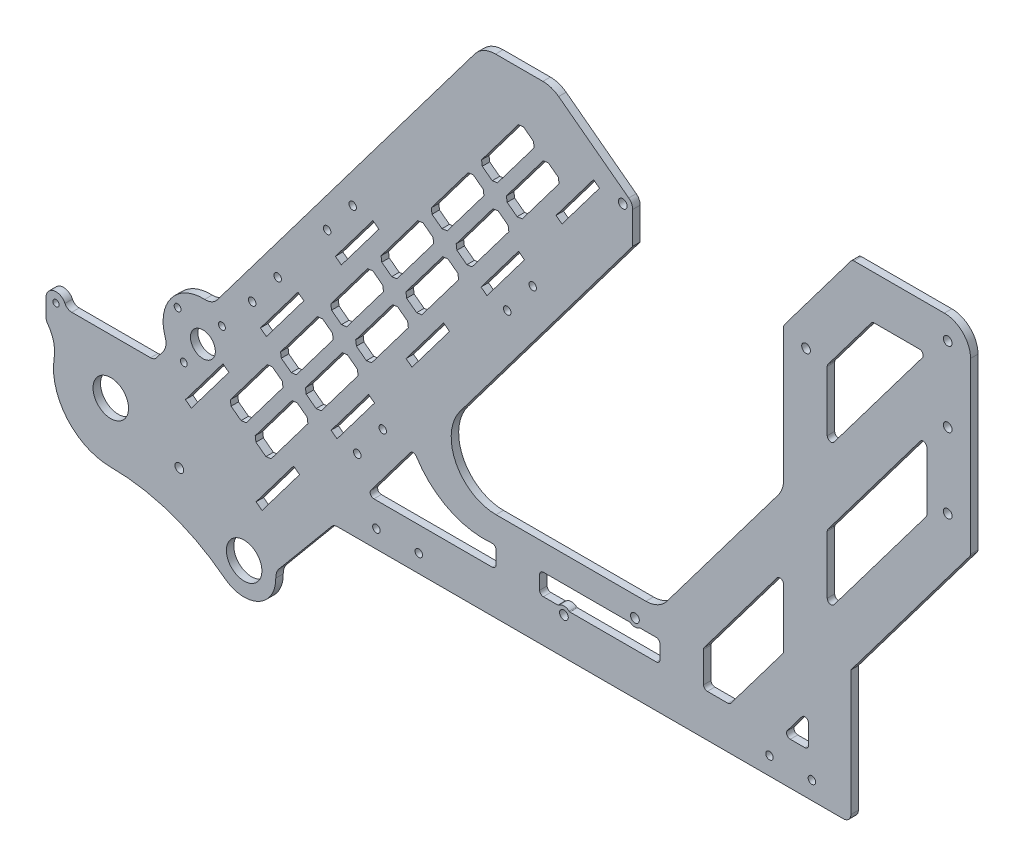
SolidWorks part; units mm, degrees
material "Liga 1060"
ref_plane "Plano frontal" through (0, 0, 0) normal (0, 0, 1) x (1, 0, 0)
ref_plane "Plano superior" through (0, 0, 0) normal (0, 1, 0) x (1, 0, 0)
ref_plane "Plano direito" through (0, 0, 0) normal (1, 0, 0) x (0, 0, -1)
sketch "Esboço1" plane through (0, 0, 0) normal (0, 0, 1) x (1, 0, 0)
  line L0 (0, 92) -> (0, 0) construction
  line L1 (0, 0) -> (52, 0)
  line L4 (231, 49.5601) -> (742, 49.5601)
  line L5 (742, 49.5601) -> (742, 441.5601)
  line L6 (742, 441.5601) -> (350.3481, 441.5601)
  line L7 (350.3481, 441.5601) -> (86.9357, 92)
  line L8 (0, 92) -> (86.9357, 92)
  line L9 (0, 92) -> (0, 0)
  circle A0 centre (52, 48) radius 14.25
  arc A1 (52, 0) -> (143.3633, -31.4562) centre (52, -148.4086) cw
  circle A2 centre (52, 48) radius 50.8 construction
  circle A3 centre (159, -11.4399) radius 25.4 construction
  arc A5 (183.9836, -6.8596) -> (231, 49.5601) centre (231, 1.7601) cw
  circle A6 centre (159, -11.4399) radius 14.25
  arc A7 (143.3633, -31.4562) -> (183.9836, -6.8596) centre (159, -11.4399) ccw
  dimension "D1" = 28.5
  dimension "D5" = 101.6
  dimension "D7" = 50.8
  dimension "D9" = 61
  dimension "D11" = 48
  dimension "D12" = 72
  dimension "D2" = 107
  dimension "D3" = 52
  dimension "D4" = 127
  dimension "D6" = 52
  dimension "D8" = 92
  dimension "D10" = 59.4399
  dimension "D13" = 742
  dimension "D16" = 86.9357
  dimension "D17" = 392
extrude "Ressalto-extrusão1" add sketch "Esboço1" along normal blind 6 contours A0 | A6 | L4 L5 L6 L7 L8 L9 L1 A1 A7 A5 region at (52, 48, 0) region at (159, -11.4399, 0)
sketch "Esboço2" plane through (0, 0, 6) normal (0, 0, 1) x (1, 0, 0)
  line L0 (183.9836, -6.8596) -> (231, 49.5601)
  arc A0 (183.9836, -6.8596) -> (231, 49.5601) centre (231, 1.7601) cw
extrude "Ressalto-extrusão2" add sketch "Esboço2" against normal through all
fillet "Filete1" radius 12 1 edges at (183.9836, -6.8596, 3)
fillet "Filete2" radius 6 2 edges at (231, 49.5601, 3) (86.9357, 92, 3)
sketch "Esboço3" plane through (0, 0, 6) normal (0, 0, 1) x (1, 0, 0)
  line L0 (52, 92) -> (0, 92)
  line L1 (0, 92) -> (0, 0)
  line L2 (52, 0) -> (0, 0)
  circle A0 centre (52, 48) radius 44 construction
  arc A1 (52, 0) -> (52, 92) centre (52, 46) cw
  arc A2 (143.3633, -31.4562) -> (52, 0) centre (52, -148.4086) ccw construction
  circle A3 centre (8, 84) radius 6.35 construction
  circle A4 centre (8, 84) radius 2.5 construction
  arc A5 (0, 76) -> (6.5667, 53.1986) centre (-21.0883, 57.5803) cw
  line M17 (0, 0) -> (52, 0)
  dimension "D1" = 12.7
  dimension "D2" = 8
  dimension "D4" = 5
  dimension "D6" = 28
  dimension "D3" = 8
  dimension "D5" = 16
extrude "Corte-extrusão1" cut sketch "Esboço3" against normal blind 10 contours A5 L1 A1 M17 | A4 region at (9.7589, 23.0045, 6)
fillet "Filete3" radius 6 1 edges at (0, 76, 3)
sketch "Esboço5" plane through (0, 0, 6) normal (0, 0, 1) x (1, 0, 0)
  line L0 (0, 92) -> (83.9442, 92) construction
  line L1 (0, 92) -> (0, 78.1284) construction
  line L2 (0, 92) -> (16, 92)
  arc A0 (0, 92) -> (16, 92) centre (8, 92) cw
  dimension "D1" = 8
extrude "Ressalto-extrusão3" add sketch "Esboço5" against normal through all
sketch "Esboço6" plane through (0, 0, 6) normal (0, 0, 1) x (1, 0, 0)
  circle A0 centre (8, 92) radius 2.5
  dimension "D1" = 5
extrude "Corte-extrusão2" cut sketch "Esboço6" against normal blind 10
fillet "Filete4" radius 6 1 edges at (16, 92, 3)
sketch "Esboço7" plane through (0, 0, 6) normal (0, 0, 1) x (1, 0, 0)
  line L0 (88.736, 94.3891) -> (168.5995, 34.2076) construction
  line L1 (88.736, 94.3891) -> (350.3481, 441.5601) construction
  line L2 (168.5995, 34.2076) -> (430.2117, 381.3786) construction
  line L3 (350.3481, 441.5601) -> (430.2117, 381.3786) construction
  line L4 (168.5995, 34.2076) -> (198.6903, 74.1394)
  line L5 (168.5995, 34.2076) -> (173.3913, 30.5967)
  line L6 (198.6903, 74.1394) -> (203.4821, 70.5285)
  line L7 (173.3913, 30.5967) -> (203.4821, 70.5285)
  line L8 (228.781, 114.0712) -> (258.8718, 154.0029)
  line L9 (228.781, 114.0712) -> (233.5728, 110.4603)
  line L10 (233.5728, 110.4603) -> (263.6636, 150.392)
  line L11 (258.8718, 154.0029) -> (263.6636, 150.392)
  line L12 (288.9625, 193.9347) -> (319.0533, 233.8665)
  line L13 (288.9625, 193.9347) -> (293.7543, 190.3238)
  line L14 (293.7543, 190.3238) -> (323.8451, 230.2556)
  line L15 (319.0533, 233.8665) -> (323.8451, 230.2556)
  line L16 (349.144, 273.7983) -> (379.2348, 313.73)
  line L17 (349.144, 273.7983) -> (353.9359, 270.1874)
  line L18 (353.9359, 270.1874) -> (384.0266, 310.1191)
  line L19 (379.2348, 313.73) -> (384.0266, 310.1191)
  line L20 (409.3255, 353.6618) -> (439.4163, 393.5936)
  line L21 (409.3255, 353.6618) -> (414.1174, 350.0509)
  line L22 (414.1174, 350.0509) -> (444.2081, 389.9827)
  line L23 (439.4163, 393.5936) -> (444.2081, 389.9827)
  line L24 (111.8964, 76.9365) -> (141.9872, 116.8682)
  line L25 (111.8964, 76.9365) -> (116.6882, 73.3256)
  line L26 (116.6882, 73.3256) -> (146.779, 113.2574)
  line L27 (141.9872, 116.8682) -> (146.779, 113.2574)
  line L28 (172.0779, 156.8) -> (202.1687, 196.7318)
  line L29 (202.1687, 196.7318) -> (206.9605, 193.1209)
  line L30 (176.8697, 153.1891) -> (206.9605, 193.1209)
  line L31 (172.0779, 156.8) -> (176.8697, 153.1891)
  line L32 (232.2594, 236.6636) -> (262.3502, 276.5954)
  line L33 (262.3502, 276.5954) -> (267.142, 272.9845)
  line L34 (237.0512, 233.0527) -> (267.142, 272.9845)
  line L35 (232.2594, 236.6636) -> (237.0512, 233.0527)
  circle A0 centre (159, -11.4399) radius 25.4 construction
  circle A1 centre (159, -11.4399) radius 30 construction
  dimension "D2" = 50.8
  dimension "D3" = 60
  dimension "D1" = 100
  dimension "D4" = 50
  dimension "D5" = 6
  dimension "D7" = 2
  dimension "D6" = 5
  dimension "D8" = 3
extrude "Corte-extrusão3" cut sketch "Esboço7" against normal through all
sketch "Esboço8" plane through (0, 0, 6) normal (0, 0, 1) x (1, 0, 0)
  circle A0 centre (711, 628) radius 14.25
  circle A2 centre (52, 48) radius 14.25 construction
  circle A3 centre (711, 628) radius 16
  dimension "D3" = 28.5
  dimension "D4" = 32
  dimension "D1" = 659
  dimension "D2" = 580
extrude "Ressalto-extrusão4" add sketch "Esboço8" against normal blind 6 separate body
sketch "Esboço9" plane through (0, 0, 0) normal (0, 0, -1) x (-1, 0, 0)
  line L0 (-742, 441.5601) -> (-350.3481, 441.5601) construction
  line L1 (-592, 441.5601) -> (-492, 441.5601)
  line L2 (-742, 49.5601) -> (-742, 441.5601) construction
  line L3 (-492, 441.5601) -> (-250.8627, 121.5601)
  line L4 (-353.9359, 270.1874) -> (-384.0266, 310.1191) construction
  line L6 (-592, 121.5601) -> (-250.8627, 121.5601)
  line L7 (-592, 441.5601) -> (-592, 121.5601)
  dimension "D3" = 320
  dimension "D1" = 150
  dimension "D2" = 100
extrude "Corte-extrusão4" cut sketch "Esboço9" against normal through all
fillet "Filete5" radius 55 1 edges at (250.8627, 121.5601, 3)
sketch "Esboço10" plane through (0, 0, 0) normal (0, 0, -1) x (-1, 0, 0)
  line L0 (-233.8102, 49.5601) -> (-742, 49.5601) construction
  line L1 (-742, 49.5601) -> (-742, 441.5601) construction
  line L2 (-646, 49.5601) -> (-742, 49.5601)
  line L3 (-742, 49.5601) -> (-742, 245.5601)
  line L4 (-742, 49.5601) -> (-742, 441.5601) construction
  line L6 (-646, 176.7664) -> (-646, 49.5601)
  arc A4 (-742, 245.5601) -> (-646, 176.7664) centre (-830.0314, 21.3346) cw
  dimension "D1" = 96
extrude "Corte-extrusão5" cut sketch "Esboço10" against normal through all
fillet "Filete8" radius 21 3 edges at (742, 441.5601, 3) (350.3481, 441.5601, 3) (492, 441.5601, 3)
sketch "Esboço12" plane through (0, 0, 6) normal (0, 0, 1) x (1, 0, 0)
  line L0 (317.2507, 209.6599) -> (466.6519, 407.922) construction
  line L1 (470.8805, 420.5601) -> (470.8805, 388.5548)
  line L2 (441.6369, 374.726) -> (466.6519, 407.922)
  arc A0 (441.6369, 374.726) -> (460.6344, 380.8766) centre (457.593, 357.8565) cw
  arc A1 (460.6344, 380.8766) -> (470.8805, 388.5548) centre (462.8805, 388.5548) ccw
  arc A2 (466.6519, 407.922) -> (449.8805, 441.5601) centre (449.8805, 420.5601) ccw construction
  arc A4 (466.6519, 407.922) -> (470.8805, 420.5601) centre (449.8805, 420.5601) ccw
  dimension "D1" = 16
extrude "Ressalto-extrusão5" add sketch "Esboço12" against normal through all
sketch "Esboço13" plane through (0, 0, 6) normal (0, 0, 1) x (1, 0, 0)
  circle A0 centre (462.8805, 388.5548) radius 2.5
  dimension "D1" = 5
extrude "Corte-extrusão7" cut sketch "Esboço13" against normal through all
sketch "Esboço14" plane through (0, 0, 6) normal (0, 0, 1) x (1, 0, 0)
  line L0 (467.695, 394.9439) -> (405.8333, 441.5601)
  line L1 (449.8805, 441.5601) -> (360.8183, 441.5601) construction
  line L2 (405.8333, 441.5601) -> (449.8805, 441.5601)
  line L3 (470.8805, 388.5548) -> (470.8805, 420.5601)
  line L4 (444.2081, 389.9827) -> (439.4163, 393.5936) construction
  arc A0 (470.8805, 388.5548) -> (467.695, 394.9439) centre (462.8805, 388.5548) ccw
  arc A1 (470.8805, 420.5601) -> (449.8805, 441.5601) centre (449.8805, 420.5601) ccw construction
  arc A2 (449.8805, 441.5601) -> (470.8805, 420.5601) centre (449.8805, 420.5601) cw
extrude "Corte-extrusão8" cut sketch "Esboço14" against normal through all
fillet "Filete10" radius 21 1 edges at (405.8333, 441.5601, 3)
fillet "Filete11" radius 21 1 edges at (646, 176.7664, 3)
fillet "Filete12" radius 21 1 edges at (742, 245.5601, 3)
sketch "Esboço16" plane through (0, 0, 6) normal (0, 0, 1) x (1, 0, 0)
  line L0 (592, 254.2646) -> (492, 121.5601)
  line L1 (592, 441.5601) -> (592, 121.5601) construction
  line L2 (592, 121.5601) -> (361.1756, 121.5601) construction
  line L3 (492, 121.5601) -> (592, 121.5601)
  line L4 (592, 121.5601) -> (592, 254.2646)
  line L5 (317.2507, 209.6599) -> (441.6369, 374.726) construction
extrude "Ressalto-extrusão6" add sketch "Esboço16" against normal through all
fillet "Filete13" radius 21 2 edges at (592, 254.2646, 3) (492, 121.5601, 3)
chamfer "Chanfro1" distance 55 angle 53 1 edges at (592, 441.5601, 3) first distance on face at (656.5, 441.5601, 3)
sketch "Esboço17" plane through (0, 0, 6) normal (0, 0, 1) x (1, 0, 0)
  line L0 (663.1982, 406.5601) -> (627, 358.5235)
  line L1 (627, 358.5235) -> (627, 300.3965)
  line L2 (627, 300.3965) -> (707, 406.5601)
  line L4 (707, 406.5601) -> (663.1982, 406.5601)
  line L5 (627, 243.9008) -> (707, 350.0644)
  line L6 (707, 350.0644) -> (707, 293.5686)
  line L7 (707, 293.5686) -> (627, 187.405)
  line L8 (627, 187.405) -> (627, 243.9008)
  line L9 (742, 259.446) -> (742, 420.5601) construction
  line L10 (592, 368.5727) -> (592, 261.2911) construction
  line L11 (647, 441.5601) -> (592, 368.5727) construction
  line L12 (721, 441.5601) -> (647, 441.5601) construction
  line L13 (646, 106.1231) -> (742, 233.5194)
  line L14 (646, 49.5601) -> (646, 168.885) construction
  line L15 (742, 233.5194) -> (742, 283.5194)
  line L16 (742, 283.5194) -> (646, 156.1231)
  line L17 (646, 156.1231) -> (646, 106.1231)
  point P19 (619.5, 405.0664)
  dimension "D1" = 35
  dimension "D2" = 35
  dimension "D3" = 34
  dimension "D4" = 35
  dimension "D5" = 34
  dimension "D6" = 34
  dimension "D7" = 34
  dimension "D8" = 50
extrude "Corte-extrusão10" cut sketch "Esboço17" against normal through all
fillet "Filete15" radius 3 11 edges at (647, 441.5601, 3) (592, 368.5727, 3) (742, 283.5194, 3) (707, 293.5686, 3) (627, 187.405, 3) (627, 243.9008, 3) (707, 350.0644, 3) (663.1982, 406.5601, 3) (627, 358.5235, 3) (627, 300.3965, 3) (707, 406.5601, 3)
sketch "Esboço20" plane through (0, 0, 6) normal (0, 0, 1) x (1, 0, 0)
  line L0 (694.4886, 220.4696) -> (646, 156.1231)
  line L1 (646, 49.5601) -> (646, 168.885) construction
  line L5 (741.3959, 282.7177) -> (694.4886, 220.4696) construction
  line L6 (646, 156.1231) -> (646, 192.1231)
  line L7 (646, 192.1231) -> (694.4886, 220.4696)
  dimension "D1" = 36
extrude "Ressalto-extrusão9" add sketch "Esboço20" against normal through all contours L7 L0 L6
sketch "Esboço21" plane through (0, 0, 6) normal (0, 0, 1) x (1, 0, 0)
  line L0 (592, 197.4542) -> (527.7473, 112.1879)
  line L1 (527.7473, 112.1879) -> (527.7473, 83.5601)
  line L2 (548.7473, 83.5601) -> (592, 140.9584)
  line L3 (592, 140.9584) -> (592, 197.4542)
  line L4 (701.6041, 342.9037) -> (627.6041, 244.7024) construction
  line L5 (592, 367.5689) -> (592, 261.2911) construction
  line L6 (632.3959, 194.5656) -> (706.3959, 292.7669) construction
  line L7 (527.7473, 83.5601) -> (548.7473, 83.5601)
  line L8 (233.8102, 49.5601) -> (646, 49.5601) construction
  line L9 (591.3199, 83.5601) -> (612, 83.5601)
  line L10 (612, 83.5601) -> (612, 111.0036)
  line L11 (612, 111.0036) -> (591.3199, 83.5601)
  line L12 (741.3959, 282.7177) -> (646, 156.1231) construction
  line L13 (646, 49.5601) -> (646, 156.1231) construction
  dimension "D1" = 34
  dimension "D2" = 21
  dimension "D3" = 34
extrude "Corte-extrusão12" cut sketch "Esboço21" against normal through all
fillet "Filete16" radius 3 8 edges at (612, 83.5601, 3) (612, 111.0036, 3) (591.3199, 83.5601, 3) (592, 197.4542, 3) (592, 140.9584, 3) (548.7473, 83.5601, 3) (527.7473, 83.5601, 3) (527.7473, 112.1879, 3)
sketch "Esboço22" plane through (0, 0, 6) normal (0, 0, 1) x (1, 0, 0)
  line L0 (295.0412, 133.8742) -> (257.1269, 83.5601)
  line L1 (257.1269, 83.5601) -> (361.1756, 83.5601)
  line L2 (361.1756, 83.5601) -> (361.1756, 100.5601)
  line L3 (396.1756, 83.5601) -> (492.7473, 83.5601)
  line L4 (492.7473, 83.5601) -> (492.7473, 100.5601)
  line L5 (492.7473, 100.5601) -> (396.1756, 100.5601)
  line L6 (396.1756, 100.5601) -> (396.1756, 83.5601)
  line L7 (481.5298, 121.5601) -> (361.1756, 121.5601) construction
  line L8 (530.7473, 83.5601) -> (547.2515, 83.5601) construction
  line L9 (527.7473, 111.1842) -> (527.7473, 86.5601) construction
  line L10 (233.5728, 110.4603) -> (263.6636, 150.392) construction
  arc A0 (295.0412, 133.8742) -> (361.1756, 100.5601) centre (351.5932, 163.8387) ccw
  dimension "D5" = 64
  dimension "D1" = 21
  dimension "D2" = 35
  dimension "D3" = 35
  dimension "D4" = 35
  dimension "D6" = 63
extrude "Corte-extrusão13" cut sketch "Esboço22" against normal through all
fillet "Filete17" radius 3 8 edges at (257.1269, 83.5601, 3) (295.0412, 133.8742, 3) (361.1756, 83.5601, 3) (361.1756, 100.5601, 3) (396.1756, 83.5601, 3) (396.1756, 100.5601, 3) (492.7473, 100.5601, 3) (492.7473, 83.5601, 3)
fillet "Filete18" radius 6 1 edges at (646, 49.5601, 3)
sketch "Esboço23" plane through (0, 0, 6) normal (0, 0, 1) x (1, 0, 0)
  line L0 (592, 367.5689) -> (592, 261.2911) construction
  line L2 (721, 441.5601) -> (648.4957, 441.5601) construction
  circle A0 centre (610, 361.5601) radius 2.5
  dimension "D1" = 5
  dimension "D2" = 18
  dimension "D3" = 80
extrude "Corte-extrusão14" cut sketch "Esboço23" against normal through all
sketch "Esboço24" plane through (0, 0, 0) normal (0, 0, -1) x (-1, 0, 0)
  line L0 (-344.047, 433.1982) -> (-88.736, 94.3891) construction
  line L1 (-133.2426, 153.4513) -> (-98.0771, 106.7852)
  arc A0 (-133.2426, 153.4513) -> (-98.0771, 106.7852) centre (-125.8978, 122.4034) cw
  circle A1 centre (-125.6123, 122.8747) radius 10 construction
  dimension "D1" = 20
extrude "Ressalto-extrusão10" add sketch "Esboço24" against normal through all
fillet "Filete19" radius 12 2 edges at (98.0771, 106.7852, 3) (133.2426, 153.4513, 3)
sketch "Esboço25" plane through (0, 0, 6) normal (0, 0, 1) x (1, 0, 0)
  circle A0 centre (125.8978, 122.4034) radius 10
  dimension "D1" = 20
extrude "Corte-extrusão15" cut sketch "Esboço25" against normal through all
sketch "Esboço26" plane through (0, 0, 6) normal (0, 0, 1) x (1, 0, 0)
  line L0 (311.9542, 152.0192) -> (470.8805, 362.9215)
  line L1 (470.8805, 362.9215) -> (470.8805, 388.5548)
  line L2 (317.2507, 209.6599) -> (441.6369, 374.726) construction
  line L3 (441.6369, 374.726) -> (317.2507, 209.6599)
  arc A0 (317.2507, 209.6599) -> (361.1756, 121.5601) centre (361.1756, 176.5601) ccw construction
  arc A1 (460.6344, 380.8766) -> (467.695, 394.9439) centre (462.8805, 388.5548) ccw construction
  arc A2 (317.2507, 209.6599) -> (311.9542, 152.0192) centre (361.1756, 176.5601) ccw
  arc A3 (441.6369, 374.726) -> (460.6344, 380.8766) centre (457.593, 357.8565) cw
  arc A4 (460.6344, 380.8766) -> (470.8805, 388.5548) centre (462.8805, 388.5548) ccw
extrude "Ressalto-extrusão11" add sketch "Esboço26" against normal blind 6
sketch "Esboço27" plane through (0, 0, 6) normal (0, 0, 1) x (1, 0, 0)
  line L0 (311.9542, 152.0192) -> (470.8805, 362.9215) construction
  line L1 (481.5298, 121.5601) -> (361.1756, 121.5601) construction
  line L2 (332.437, 179.2008) -> (311.9542, 152.0192)
  arc A0 (361.1756, 121.5601) -> (332.437, 179.2008) centre (361.1756, 157.5447) cw
  arc A1 (311.9542, 152.0192) -> (361.1756, 121.5601) centre (361.1756, 176.5601) ccw
extrude "Ressalto-extrusão12" add sketch "Esboço27" against normal blind 6
sketch "Esboço28" [suppressed] plane through (0, 0, 6) normal (0, 0, 1) x (1, 0, 0)
  line L0 (93.8642, 101.1945) -> (137.4555, 159.0421)
  circle A0 centre (125.8978, 122.4034) radius 10
  arc A1 (93.8642, 101.1945) -> (137.4555, 159.0421) centre (127.1672, 121.4469) cw
extrude "Ressalto-extrusão13" [suppressed] add sketch "Esboço28" against normal through all
sketch "Esboço29" [suppressed] plane through (0, 0, 6) normal (0, 0, 1) x (1, 0, 0)
  line L0 (93.8642, 101.1945) -> (137.4555, 159.0421)
  arc A0 (93.8642, 101.1945) -> (137.4555, 159.0421) centre (127.1672, 121.4469) cw
extrude "Corte-extrusão16" [suppressed] cut sketch "Esboço29" against normal through all
sketch "Esboço30" plane through (0, 0, 6) normal (0, 0, 1) x (1, 0, 0)
  circle A0 centre (462.8805, 388.5548) radius 3.5
  circle A1 centre (610, 361.5601) radius 3.5
  dimension "D1" = 7
extrude "Corte-extrusão17" cut sketch "Esboço30" against normal through all
sketch "Esboço31" [suppressed] plane through (0, 0, 6) normal (0, 0, 1) x (1, 0, 0)
  circle A0 centre (462.8805, 388.5548) radius 3.5
  circle A1 centre (610, 361.5601) radius 3.5
  dimension "D1" = 7
extrude "Corte-extrusão18" [suppressed] cut sketch "Esboço31" against normal through all
sketch "Esboço32" plane through (0, 0, 6) normal (0, 0, 1) x (1, 0, 0)
  circle A0 centre (472.6657, 105.5463) radius 3.5
  circle A1 centre (415.6657, 79.0463) radius 3.5
extrude "Corte-extrusão19" cut sketch "Esboço32" against normal through all
sketch "Esboço33" plane through (0, 0, 6) normal (0, 0, 1) x (1, 0, 0)
  circle A0 centre (472.6657, 105.5463) radius 6.35
  circle A1 centre (415.6657, 79.0463) radius 6.35
  circle A2 centre (415.6657, 79.0463) radius 3.5
  circle A3 centre (472.6657, 105.5463) radius 3.5
  dimension "D1" = 12.7
extrude "Ressalto-extrusão14" add sketch "Esboço33" against normal through all
fillet "Filete20" radius 1 4 edges at (468.7337, 100.5601, 3) (476.5976, 100.5601, 3) (411.1993, 83.5601, 3) (420.132, 83.5601, 3)
sketch "Esboço34" plane through (0, 0, 6) normal (0, 0, 1) x (1, 0, 0)
  line L0 (125.8978, 122.4034) -> (105.6124, 137.6895) construction
  line L1 (146.779, 113.2574) -> (141.9872, 116.8682) construction
  circle A0 centre (125.8978, 122.4034) radius 25.4 construction
  circle A1 centre (105.6124, 137.6895) radius 2.75
  circle A2 centre (141.1839, 142.6888) radius 2.75
  circle A3 centre (146.1831, 107.1173) radius 2.75
  circle A4 centre (110.6117, 102.1181) radius 2.75
  point P16 (125.8978, 122.4034)
  dimension "D1" = 50.8
  dimension "D2" = 5.5
  dimension "D3" = 4
extrude "Corte-extrusão20" cut sketch "Esboço34" against normal through all
sketch "Esboço35" plane through (0, 0, 6) normal (0, 0, 1) x (1, 0, 0)
  circle A0 centre (146.1831, 107.1173) radius 2.75
extrude "Ressalto-extrusão15" add sketch "Esboço35" against normal through all
sketch "Esboço36" [suppressed] plane through (0, 0, 6) normal (0, 0, 1) x (1, 0, 0)
  circle A0 centre (656.9174, 423.7644) radius 11
  dimension "D3" = 22
extrude "Corte-extrusão21" [suppressed] cut sketch "Esboço36" against normal through all
sketch "Esboço37" plane through (0, 0, 6) normal (0, 0, 1) x (1, 0, 0)
  circle A0 centre (265.1625, 63.8601) radius 3
  circle A1 centre (299.1625, 63.8601) radius 3
  circle A2 centre (580.6625, 63.8601) radius 3
  circle A3 centre (614.6625, 63.8601) radius 3
extrude "Corte-extrusão22" cut sketch "Esboço37" against normal through all
sketch "Esboço38" [suppressed] plane through (0, 0, 6) normal (0, 0, 1) x (1, 0, 0)
  circle A1 centre (580.6625, 63.8601) radius 3
  circle A2 centre (614.6625, 63.8601) radius 3
  circle A3 centre (265.1625, 63.8601) radius 3
  circle A4 centre (299.1625, 63.8601) radius 3
extrude "Corte-extrusão23" [suppressed] cut sketch "Esboço38" against normal through all
sketch "Esboço39" [suppressed] plane through (0, 0, 6) normal (0, 0, 1) x (1, 0, 0)
  circle A0 centre (230.2462, 98.4918) radius 10
  dimension "D1" = 20
extrude "Corte-extrusão24" [suppressed] cut sketch "Esboço39" against normal through all
sketch "Esboço40" [suppressed] plane through (0, 0, 6) normal (0, 0, 1) x (1, 0, 0)
  line L0 (230.2462, 98.4918) -> (245.5323, 118.7772) construction
  line L1 (233.5728, 110.4603) -> (263.6636, 150.392) construction
  circle A0 centre (230.2462, 98.4918) radius 25.4 construction
  circle A1 centre (245.5323, 118.7772) radius 2.75
  circle A2 centre (250.5315, 83.2057) radius 2.75
  circle A3 centre (214.9601, 78.2065) radius 2.75
  point P13 (230.2462, 98.4918)
  dimension "D1" = 50.8
  dimension "D2" = 5.5
  dimension "D3" = 3
extrude "Corte-extrusão25" [suppressed] cut sketch "Esboço40" against normal through all
sketch "Esboço41" plane through (0, 0, 0) normal (0, 0, -1) x (-1, 0, 0)
  circle A0 centre (-723.7, 423.5863) radius 3.5
  circle A1 centre (-723.7, 363.5863) radius 3.5
  circle A2 centre (-723.7, 303.5863) radius 3.5
  dimension "D1" = 7
extrude "Corte-extrusão26" cut sketch "Esboço41" against normal through all
sketch "Esboço42" [suppressed] plane through (0, 0, 0) normal (0, 0, -1) x (-1, 0, 0)
  circle A0 centre (-656.9174, 423.7644) radius 28
  circle A1 centre (-656.9174, 423.7644) radius 11
  dimension "D1" = 56
extrude "Ressalto-extrusão16" [suppressed] add sketch "Esboço42" against normal through all contours A1 | A0
fillet "Filete21" [suppressed] radius 13
sketch "Esboço43" [suppressed] plane through (0, 0, 6) normal (0, 0, 1) x (1, 0, 0)
  circle A0 centre (723.7, 423.5863) radius 3.5
  circle A1 centre (723.7, 363.5863) radius 3.5
  circle A2 centre (723.7, 303.5863) radius 3.5
extrude "Corte-extrusão27" [suppressed] cut sketch "Esboço43" against normal through all
sketch "Esboço44" plane through (0, 0, 6) normal (0, 0, 1) x (1, 0, 0)
  circle A0 centre (711, 628) radius 16
extrude "Corte-extrusão28" cut sketch "Esboço44" against normal blind 10
sketch "Esboço45" plane through (0, 0, 6) normal (0, 0, 1) x (1, 0, 0)
  line L0 (176.8697, 153.1891) -> (228.781, 114.0712) construction
  line L1 (188.2588, 148.3633) -> (217.7477, 187.4964)
  line L2 (188.8493, 144.1619) -> (196.8356, 138.1438)
  line L3 (221.9491, 188.0869) -> (229.9354, 182.0687)
  line L4 (201.037, 138.7342) -> (230.5259, 177.8674)
  line L5 (237.7136, 172.451) -> (206.4192, 130.922)
  line L6 (241.915, 173.0415) -> (249.9013, 167.0233)
  line L7 (206.4192, 130.922) -> (219.1974, 121.2929)
  line L8 (250.4918, 162.822) -> (219.1974, 121.2929)
  line L9 (188.2588, 148.3633) -> (188.8493, 144.1619)
  line L10 (196.8356, 138.1438) -> (201.037, 138.7342)
  line L11 (217.7477, 187.4964) -> (221.9491, 188.0869)
  line L12 (229.9354, 182.0687) -> (230.5259, 177.8674)
  line L13 (237.7136, 172.451) -> (241.915, 173.0415)
  line L14 (249.9013, 167.0233) -> (250.4918, 162.822)
  line L71 (228.5804, 201.8718) -> (258.0693, 241.005)
  line L72 (258.0693, 241.005) -> (262.2707, 241.5954)
  line L73 (228.5804, 201.8718) -> (229.1709, 197.6705)
  line L74 (229.1709, 197.6705) -> (237.1572, 191.6523)
  line L75 (237.1572, 191.6523) -> (241.3586, 192.2428)
  line L76 (241.3586, 192.2428) -> (270.8475, 231.3759)
  line L77 (270.257, 235.5773) -> (270.8475, 231.3759)
  line L78 (262.2707, 241.5954) -> (270.257, 235.5773)
  line L79 (278.0352, 225.9596) -> (246.7408, 184.4306)
  line L80 (278.0352, 225.9596) -> (282.2366, 226.5501)
  line L81 (282.2366, 226.5501) -> (290.2229, 220.5319)
  line L82 (290.2229, 220.5319) -> (290.8134, 216.3306)
  line L83 (290.8134, 216.3306) -> (259.519, 174.8015)
  line L84 (246.7408, 184.4306) -> (259.519, 174.8015)
  line L85 (268.902, 255.3804) -> (298.3909, 294.5136)
  line L86 (298.3909, 294.5136) -> (302.5923, 295.104)
  line L87 (268.902, 255.3804) -> (269.4925, 251.1791)
  line L88 (269.4925, 251.1791) -> (277.4788, 245.1609)
  line L89 (277.4788, 245.1609) -> (281.6802, 245.7514)
  line L90 (281.6802, 245.7514) -> (311.1691, 284.8845)
  line L91 (310.5787, 289.0859) -> (311.1691, 284.8845)
  line L92 (302.5923, 295.104) -> (310.5787, 289.0859)
  line L93 (318.3568, 279.4682) -> (287.0625, 237.9391)
  line L94 (318.3568, 279.4682) -> (322.5582, 280.0586)
  line L95 (322.5582, 280.0586) -> (330.5445, 274.0405)
  line L96 (330.5445, 274.0405) -> (331.135, 269.8391)
  line L97 (331.135, 269.8391) -> (299.8406, 228.3101)
  line L98 (287.0625, 237.9391) -> (299.8406, 228.3101)
  line L99 (309.2236, 308.889) -> (338.7126, 348.0221)
  line L100 (338.7126, 348.0221) -> (342.9139, 348.6126)
  line L101 (309.2236, 308.889) -> (309.8141, 304.6876)
  line L102 (309.8141, 304.6876) -> (317.8004, 298.6695)
  line L103 (317.8004, 298.6695) -> (322.0018, 299.26)
  line L104 (322.0018, 299.26) -> (351.4907, 338.3931)
  line L105 (350.9003, 342.5945) -> (351.4907, 338.3931)
  line L106 (342.9139, 348.6126) -> (350.9003, 342.5945)
  line L107 (358.6784, 332.9768) -> (327.3841, 291.4477)
  line L108 (358.6784, 332.9768) -> (362.8798, 333.5672)
  line L109 (362.8798, 333.5672) -> (370.8661, 327.5491)
  line L110 (370.8661, 327.5491) -> (371.4566, 323.3477)
  line L111 (371.4566, 323.3477) -> (340.1622, 281.8187)
  line L112 (327.3841, 291.4477) -> (340.1622, 281.8187)
  line L113 (349.5452, 362.3976) -> (379.0342, 401.5307)
  line L114 (379.0342, 401.5307) -> (383.2355, 402.1212)
  line L115 (349.5452, 362.3976) -> (350.1357, 358.1962)
  line L116 (350.1357, 358.1962) -> (358.122, 352.1781)
  line L117 (358.122, 352.1781) -> (362.3234, 352.7685)
  line L118 (362.3234, 352.7685) -> (391.8123, 391.9017)
  line L119 (391.2219, 396.103) -> (391.8123, 391.9017)
  line L120 (383.2355, 402.1212) -> (391.2219, 396.103)
  line L121 (399, 386.4853) -> (367.7057, 344.9563)
  line L122 (399, 386.4853) -> (403.2014, 387.0758)
  line L123 (403.2014, 387.0758) -> (411.1878, 381.0577)
  line L124 (411.1878, 381.0577) -> (411.7782, 376.8563)
  line L125 (411.7782, 376.8563) -> (380.4838, 335.3273)
  line L126 (367.7057, 344.9563) -> (380.4838, 335.3273)
  line L127 (188.2588, 148.3633) -> (217.7477, 187.4964)
  line L128 (217.7477, 187.4964) -> (221.9491, 188.0869)
  line L129 (188.2588, 148.3633) -> (188.8493, 144.1619)
  line L130 (188.8493, 144.1619) -> (196.8356, 138.1438)
  line L131 (196.8356, 138.1438) -> (201.037, 138.7342)
  line L132 (201.037, 138.7342) -> (230.5259, 177.8674)
  line L133 (229.9354, 182.0687) -> (230.5259, 177.8674)
  line L134 (221.9491, 188.0869) -> (229.9354, 182.0687)
  line L135 (237.7136, 172.451) -> (206.4192, 130.922)
  line L136 (237.7136, 172.451) -> (241.915, 173.0415)
  line L137 (241.915, 173.0415) -> (249.9013, 167.0233)
  line L138 (249.9013, 167.0233) -> (250.4918, 162.822)
  line L139 (250.4918, 162.822) -> (219.1974, 121.2929)
  line L140 (206.4192, 130.922) -> (219.1974, 121.2929)
  line L141 (228.5804, 201.8718) -> (258.0693, 241.005)
  line L142 (258.0693, 241.005) -> (262.2707, 241.5954)
  line L143 (228.5804, 201.8718) -> (229.1709, 197.6705)
  line L144 (229.1709, 197.6705) -> (237.1572, 191.6523)
  line L145 (237.1572, 191.6523) -> (241.3586, 192.2428)
  line L146 (241.3586, 192.2428) -> (270.8475, 231.3759)
  line L147 (270.257, 235.5773) -> (270.8475, 231.3759)
  line L148 (262.2707, 241.5954) -> (270.257, 235.5773)
  line L149 (278.0352, 225.9596) -> (246.7408, 184.4306)
  line L150 (278.0352, 225.9596) -> (282.2366, 226.5501)
  line L151 (282.2366, 226.5501) -> (290.2229, 220.5319)
  line L152 (290.2229, 220.5319) -> (290.8134, 216.3306)
  line L153 (290.8134, 216.3306) -> (259.519, 174.8015)
  line L154 (246.7408, 184.4306) -> (259.519, 174.8015)
  line L155 (268.902, 255.3804) -> (298.3909, 294.5136)
  line L156 (298.3909, 294.5136) -> (302.5923, 295.104)
  line L157 (268.902, 255.3804) -> (269.4925, 251.1791)
  line L158 (269.4925, 251.1791) -> (277.4788, 245.1609)
  line L159 (277.4788, 245.1609) -> (281.6802, 245.7514)
  line L160 (281.6802, 245.7514) -> (311.1691, 284.8845)
  line L161 (310.5787, 289.0859) -> (311.1691, 284.8845)
  line L162 (302.5923, 295.104) -> (310.5787, 289.0859)
  line L163 (318.3568, 279.4682) -> (287.0625, 237.9391)
  line L164 (318.3568, 279.4682) -> (322.5582, 280.0586)
  line L165 (322.5582, 280.0586) -> (330.5445, 274.0405)
  line L166 (330.5445, 274.0405) -> (331.135, 269.8391)
  line L167 (331.135, 269.8391) -> (299.8406, 228.3101)
  line L168 (287.0625, 237.9391) -> (299.8406, 228.3101)
  line L169 (309.2236, 308.889) -> (338.7126, 348.0221)
  line L170 (338.7126, 348.0221) -> (342.9139, 348.6126)
  line L171 (309.2236, 308.889) -> (309.8141, 304.6876)
  line L172 (309.8141, 304.6876) -> (317.8004, 298.6695)
  line L173 (317.8004, 298.6695) -> (322.0018, 299.26)
  line L174 (322.0018, 299.26) -> (351.4907, 338.3931)
  line L175 (350.9003, 342.5945) -> (351.4907, 338.3931)
  line L176 (342.9139, 348.6126) -> (350.9003, 342.5945)
  line L177 (358.6784, 332.9768) -> (327.3841, 291.4477)
  line L178 (358.6784, 332.9768) -> (362.8798, 333.5672)
  line L179 (362.8798, 333.5672) -> (370.8661, 327.5491)
  line L180 (370.8661, 327.5491) -> (371.4566, 323.3477)
  line L181 (371.4566, 323.3477) -> (340.1622, 281.8187)
  line L182 (327.3841, 291.4477) -> (340.1622, 281.8187)
  line L183 (147.9372, 94.8547) -> (177.4261, 133.9878)
  line L184 (177.4261, 133.9878) -> (181.6275, 134.5783)
  line L185 (147.9372, 94.8547) -> (148.5277, 90.6533)
  line L186 (148.5277, 90.6533) -> (156.514, 84.6352)
  line L187 (156.514, 84.6352) -> (160.7154, 85.2256)
  line L188 (160.7154, 85.2256) -> (190.2043, 124.3588)
  line L189 (189.6138, 128.5601) -> (190.2043, 124.3588)
  line L190 (181.6275, 134.5783) -> (189.6138, 128.5601)
  line L191 (197.392, 118.9424) -> (166.0976, 77.4134)
  line L192 (197.392, 118.9424) -> (201.5934, 119.5329)
  line L193 (201.5934, 119.5329) -> (209.5797, 113.5148)
  line L194 (209.5797, 113.5148) -> (210.1702, 109.3134)
  line L195 (210.1702, 109.3134) -> (178.8758, 67.7844)
  line L196 (166.0976, 77.4134) -> (178.8758, 67.7844)
  line L197 (271.2563, 147.1748) -> (239.9619, 105.6457)
  line L198 (271.2563, 147.1748) -> (275.4577, 147.7653)
  line L199 (275.4577, 147.7653) -> (283.444, 141.7471)
  line L200 (283.444, 141.7471) -> (284.0345, 137.5458)
  line L201 (284.0345, 137.5458) -> (252.7401, 96.0167)
  line L202 (239.9619, 105.6457) -> (252.7401, 96.0167)
  line L203 (311.5779, 200.6834) -> (280.2835, 159.1543)
  line L204 (280.2835, 159.1543) -> (293.0617, 149.5253)
  line L205 (324.3561, 191.0543) -> (293.0617, 149.5253)
  line L206 (323.7656, 195.2557) -> (324.3561, 191.0543)
  line L207 (315.7793, 201.2738) -> (323.7656, 195.2557)
  line L208 (311.5779, 200.6834) -> (315.7793, 201.2738)
  line L209 (351.8995, 254.192) -> (320.6051, 212.6629)
  line L210 (320.6051, 212.6629) -> (333.3833, 203.0339)
  line L211 (364.6777, 244.5629) -> (333.3833, 203.0339)
  line L212 (364.0872, 248.7643) -> (364.6777, 244.5629)
  line L213 (356.1009, 254.7824) -> (364.0872, 248.7643)
  line L214 (351.8995, 254.192) -> (356.1009, 254.7824)
  line L215 (392.2211, 307.7005) -> (360.9268, 266.1715)
  line L216 (360.9268, 266.1715) -> (373.7049, 256.5424)
  line L217 (404.9993, 298.0715) -> (373.7049, 256.5424)
  line L218 (404.4088, 302.2728) -> (404.9993, 298.0715)
  line L219 (396.4225, 308.291) -> (404.4088, 302.2728)
  line L220 (392.2211, 307.7005) -> (396.4225, 308.291)
  line L221 (432.5427, 361.2091) -> (401.2484, 319.6801)
  line L222 (401.2484, 319.6801) -> (414.0265, 310.051)
  line L223 (445.3209, 351.5801) -> (414.0265, 310.051)
  line L224 (444.7304, 355.7814) -> (445.3209, 351.5801)
  line L225 (436.7441, 361.7996) -> (444.7304, 355.7814)
  line L226 (432.5427, 361.2091) -> (436.7441, 361.7996)
  point P3 (186.4534, 145.9674)
  point P4 (219.5532, 189.8923)
  point P5 (239.5191, 174.8469)
  point P8 (232.3313, 180.2633)
  point P9 (199.2315, 136.3383)
  point P13 (252.2972, 165.2179)
  dimension "D2" = 16
  dimension "D3" = 12
  dimension "D4" = 12
  dimension "D5" = 55
  dimension "D6" = 55
  dimension "D8" = 5
  dimension "D7" = 2
  dimension "D10" = 2
extrude "Corte-extrusão29" cut sketch "Esboço45" against normal through all contours L190 L184 L183 L185 L186 L187 L188 L189 | L191 L196 L195 L194 L193 L192 | L12 L3 L11 L1 L9 L2 L10 L4 | L14 L6 L13 L5 L7 L8 | L79 L84 L83 L82 L81 L80 | L78 L72 L71 L73 L74 L75 L76 L77 | L92 L86 L85 L87 L88 L89 L90 L91 | L93 L98 L97 L96 L95 L94 | L120 L114 L113 L115 L116 L117 L118 L119 | L121 L126 L125 L124 L123 L122 | L106 L100 L99 L101 L102 L103 L104 L105 | L107 L112 L111 L110 L109 L108 region at (209.3923, 163.1153, 6) region at (229.1934, 147.8513, 6) region at (249.714, 216.6239, 6) region at (269.5151, 201.3598, 6) region at (290.0356, 270.1325, 6) region at (309.8367, 254.8684, 6) region at (330.3572, 323.641, 6) region at (350.1583, 308.377, 6) region at (370.6788, 377.1496, 6) region at (390.4799, 361.8856, 6) region at (169.0707, 109.6067, 6) region at (188.8718, 94.3427, 6)
sketch "Esboço46" plane through (0, 0, 6) normal (0, 0, 1) x (1, 0, 0)
  circle A0 centre (390.6326, 295.1241) radius 3
  circle A1 centre (370.1709, 267.9705) radius 3
  circle A2 centre (249.8079, 108.2434) radius 3
  circle A3 centre (270.2696, 135.397) radius 3
  circle A4 centre (165.4719, 171.7951) radius 3
  circle A5 centre (185.9337, 198.9487) radius 3
  circle A6 centre (225.6534, 251.6586) radius 3
  circle A7 centre (246.1152, 278.8122) radius 3
extrude "Corte-extrusão30" cut sketch "Esboço46" against normal through all
sketch "Esboço48" plane through (0, 0, 6) normal (0, 0, 1) x (1, 0, 0)
  circle A0 centre (107, 27) radius 3.5
  circle A1 centre (52, 48) radius 14.25 construction
  dimension "D2" = 21
  dimension "D3" = 7
  dimension "D1" = 55
extrude "Corte-extrusão31" cut sketch "Esboço48" against normal through all
chamfer "Chanfro2" distance 3 angle 45 12 edges at (367.7057, 344.9563, 3) (380.4838, 335.3273, 3) (340.1622, 281.8187, 3) (327.3841, 291.4477, 3) (299.8406, 228.3101, 3) (287.0625, 237.9391, 3) (259.519, 174.8015, 3) (246.7408, 184.4306, 3) (206.4192, 130.922, 3) (219.1974, 121.2929, 3) (178.8758, 67.7844, 3) (166.0976, 77.4134, 3)
